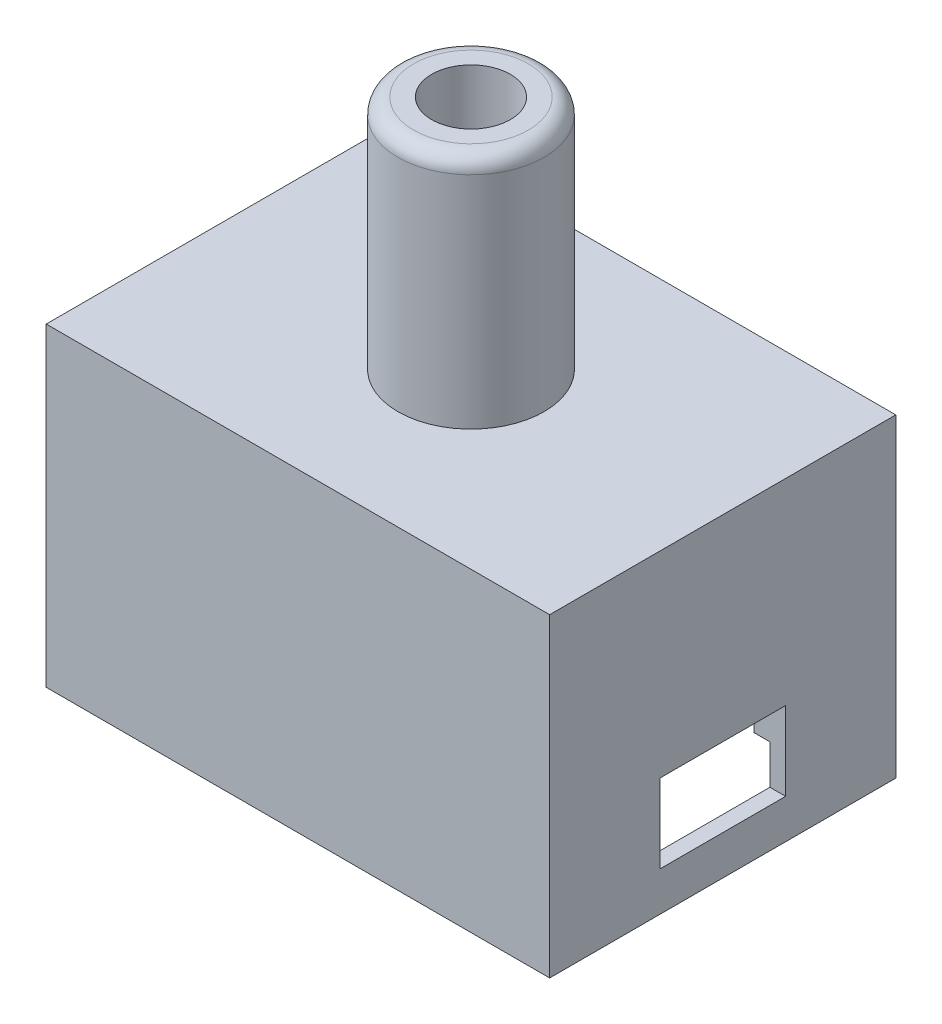
SolidWorks part; units mm, degrees
ref_plane "Front Plane" through (0, 0, 0) normal (0, 0, 1) x (1, 0, 0)
ref_plane "Top Plane" through (0, 0, 0) normal (0, 1, 0) x (1, 0, 0)
ref_plane "Right Plane" through (0, 0, 0) normal (1, 0, 0) x (0, 0, -1)
sketch "Sketch1" plane through (0, 0, 0) normal (0, 1, 0) x (1, 0, 0)
  line L1 (-16, -11) -> (16, -11)
  line L2 (-16, -11) -> (-16, 11)
  line L3 (-16, 11) -> (16, 11)
  line L4 (16, -11) -> (16, 11)
  line L5 (-16, -11) -> (16, 11) construction
  line L6 (-16, 11) -> (16, -11) construction
  point P0 (0, 0)
  dimension "D1" = 32
  dimension "D2" = 22
extrude "Boss-Extrude1" add sketch "Sketch1" along normal blind 20
sketch "Sketch2" plane through (0, 20, 0) normal (0, 1, 0) x (1, 0, 0)
  circle A0 centre (0, 0) radius 4.65
  dimension "D1" = 9.3
extrude "Boss-Extrude2" add sketch "Sketch2" along normal blind 15
sketch "Sketch3" plane through (0, 0, 0) normal (0, -1, 0) x (1, 0, 0)
  line L3 (15, -10) -> (-15, -10)
  line L4 (15, -10) -> (15, 10)
  line L5 (15, 10) -> (-15, 10)
  line L6 (-15, -10) -> (-15, 10)
  line L7 (15, -10) -> (-15, 10) construction
  line L8 (15, 10) -> (-15, -10) construction
  point P5 (0, 0)
  dimension "D1" = 20
  dimension "D2" = 30
extrude "Cut-Extrude1" cut sketch "Sketch3" against normal offset from surface (19 mm away) 1 up to face at (0, 20, 4.65)
sketch "Sketch4" plane through (0, 19, 0) normal (0, -1, 0) x (1, 0, 0)
  circle A0 centre (0, 0) radius 2.5
  dimension "D1" = 5
extrude "Cut-Extrude2" cut sketch "Sketch4" against normal through all
fillet "Fillet1" radius 1 1 edges at (0, 35, 4.65)
fillet "Fillet2" radius 1 1 edges at (0, 19, -2.5)
sketch "Sketch5" plane through (0, 19, 0) normal (0, -1, 0) x (1, 0, 0)
  line L5 (14, -9) -> (-14, -9)
  line L6 (14, -9) -> (14, 9)
  line L7 (14, 9) -> (-14, 9)
  line L8 (-14, -9) -> (-14, 9)
  line L9 (14, -9) -> (-14, 9) construction
  line L10 (14, 9) -> (-14, -9) construction
  line L11 (15, -10) -> (-15, -10)
  line L12 (15, -10) -> (15, 10)
  line L13 (15, 10) -> (-15, 10)
  line L14 (-15, -10) -> (-15, 10)
  line L15 (15, -10) -> (-15, 10) construction
  line L16 (15, 10) -> (-15, -10) construction
  point P5 (0, 0)
  point P6 (0, 0)
extrude "Boss-Extrude3" add sketch "Sketch5" along normal blind 14
sketch "Sketch8" plane through (16, 0, 0) normal (1, 0, 0) x (0, 0, -1)
  line L0 (10, 5) -> (-10, 5) construction
  line L1 (4, 2.5) -> (-4, 2.5)
  line L2 (4, 2.5) -> (4, 7.5)
  line L3 (4, 7.5) -> (-4, 7.5)
  line L4 (-4, 2.5) -> (-4, 7.5)
  line L5 (4, 2.5) -> (-4, 7.5) construction
  line L6 (4, 7.5) -> (-4, 2.5) construction
  point P0 (0, 5)
  dimension "D1" = 8
  dimension "D2" = 5
extrude "Cut-Extrude3" cut sketch "Sketch8" against normal up to surface (2 mm away) up to face at (14, 12, 0)
